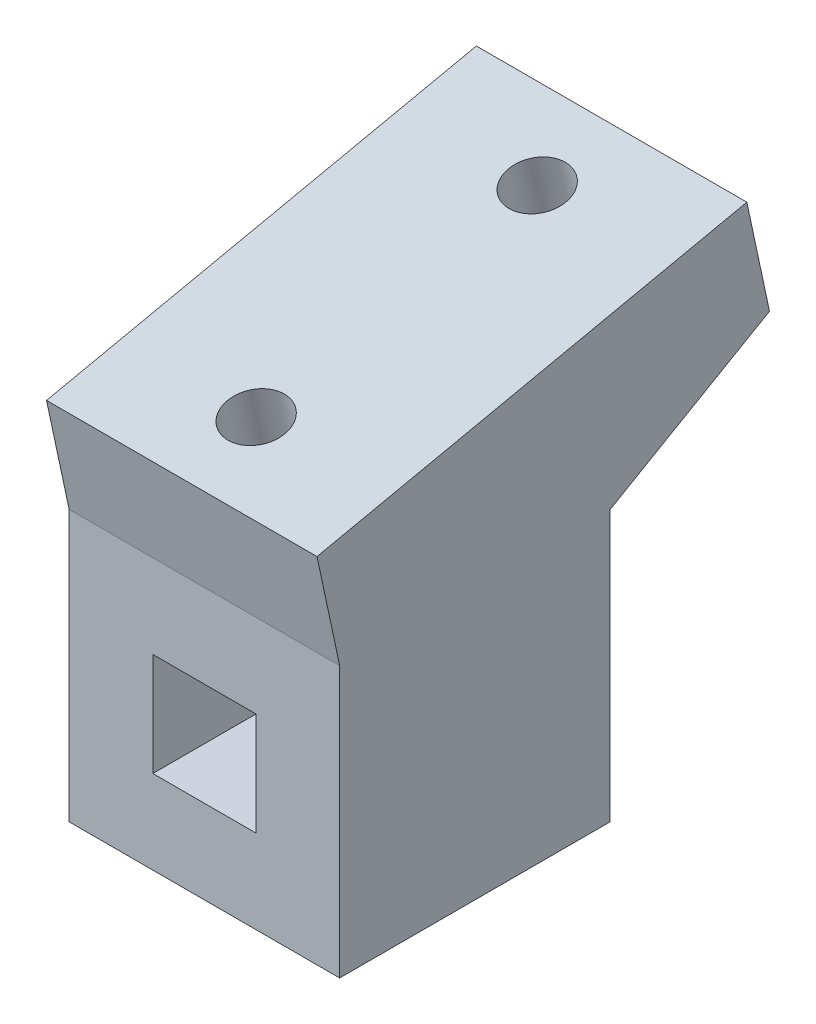
SolidWorks part; units mm, degrees
ref_plane "前视基准面" through (0, 0, 0) normal (0, 0, 1) x (1, 0, 0)
ref_plane "上视基准面" through (0, 0, 0) normal (0, 1, 0) x (1, 0, 0)
ref_plane "右视基准面" through (0, 0, 0) normal (1, 0, 0) x (0, 0, -1)
sketch "草图1" plane through (0, 0, 0) normal (0, 1, 0) x (1, 0, 0)
  line L1 (0, 0) -> (8, 0)
  line L2 (0, 0) -> (0, 8)
  line L3 (0, 8) -> (8, 8)
  line L4 (8, 0) -> (8, 8)
  dimension "D1" = 8
  dimension "D2" = 8
extrude "凸台-拉伸1" add sketch "草图1" along normal blind 7.5
sketch "草图2" plane through (0, 7.5, 0) normal (0, 1, 0) x (1, 0, 0)
  line L4 (0, 8) -> (0, 0)
  line L5 (0, 0) -> (8, 0)
  line L6 (8, 0) -> (8, 8)
  line L7 (8, 8) -> (0, 8)
  line L8 (0, 8) -> (0, 0)
  line L9 (0, 0) -> (8, 0)
  line L10 (8, 0) -> (8, 8)
  line L11 (8, 8) -> (0, 8)
  dimension "D1" = 0
extrude "凸台-拉伸2" add sketch "草图2" along normal blind 0.5
sketch "草图3" plane through (8, 0, 0) normal (1, 0, 0) x (0, 0, -1)
  line L0 (8, 8) -> (12.7121, 10.7206)
  line L1 (12.7121, 10.7206) -> (0, 8)
  line L2 (0, 8) -> (-0.6697, 11.1291)
  line L3 (-0.6697, 11.1291) -> (12.0425, 13.8497)
  line L4 (12.0425, 13.8497) -> (12.7121, 10.7206)
  line L5 (8, 8) -> (8, 0) construction
  line M8 (8, 8) -> (0, 8)
  dimension "D1" = 120
  dimension "D2" = 13
  dimension "D3" = 3.2
extrude "凸台-拉伸3" add sketch "草图3" against normal up to surface (8 mm away) contours L4 L3 L2 L1 | L0 L1 M8 region at (8, 8.9069, -6.904) region at (8, 10.9248, -6.0212) up to face at (0, 4, -4)
sketch "草图4" plane through (0, 10.7788, 2.3068) normal (0, 0.9779, 0.2093) x (1, 0, 0)
  line L0 (4, 1.6742) -> (4, 14.6742) construction
  line L1 (0, 1.6742) -> (8, 1.6742) construction
  line L2 (0, 14.6742) -> (8, 14.6742) construction
  line L3 (8, 8.1742) -> (0, 8.1742) construction
  line L4 (8, 1.6742) -> (8, 14.6742) construction
  line L5 (0, 14.6742) -> (0, 1.6742) construction
  circle A0 centre (4, 3.9242) radius 0.85
  circle A1 centre (4, 12.4242) radius 0.85
  dimension "D1" = 1.7
  dimension "D2" = 8.5
extrude "凸台-拉伸4" add sketch "草图4" against normal blind 4
extrude "切除-拉伸1" cut sketch "草图4<2>" against normal blind 4.2
sketch "草图4<2>" plane through (0, 10.7788, 2.3068) normal (0, 0.9779, 0.2093) x (1, 0, 0) same geometry as "草图4"
sketch "草图5" plane through (0, 0, -8) normal (0, 0, -1) x (-1, 0, 0)
  line L1 (-5.525, 5.525) -> (-2.475, 5.525)
  line L2 (-5.525, 5.525) -> (-5.525, 2.475)
  line L3 (-5.525, 2.475) -> (-2.475, 2.475)
  line L4 (-2.475, 5.525) -> (-2.475, 2.475)
  line L6 (0, 0) -> (-8, 0)
  line L7 (0, 0) -> (0, 8)
  line L8 (-8, 8) -> (0, 8) construction
  line L9 (0, 8) -> (0, 0) construction
  point P8 (0, 4)
  point P14 (-2.475, 4)
  point P15 (-4, 0)
  point P16 (-4, 2.475)
  dimension "D1" = 3.05
  dimension "D2" = 3.05
extrude "切除-拉伸2" cut sketch "草图5" against normal through all contours L2 L1 L4 L3
